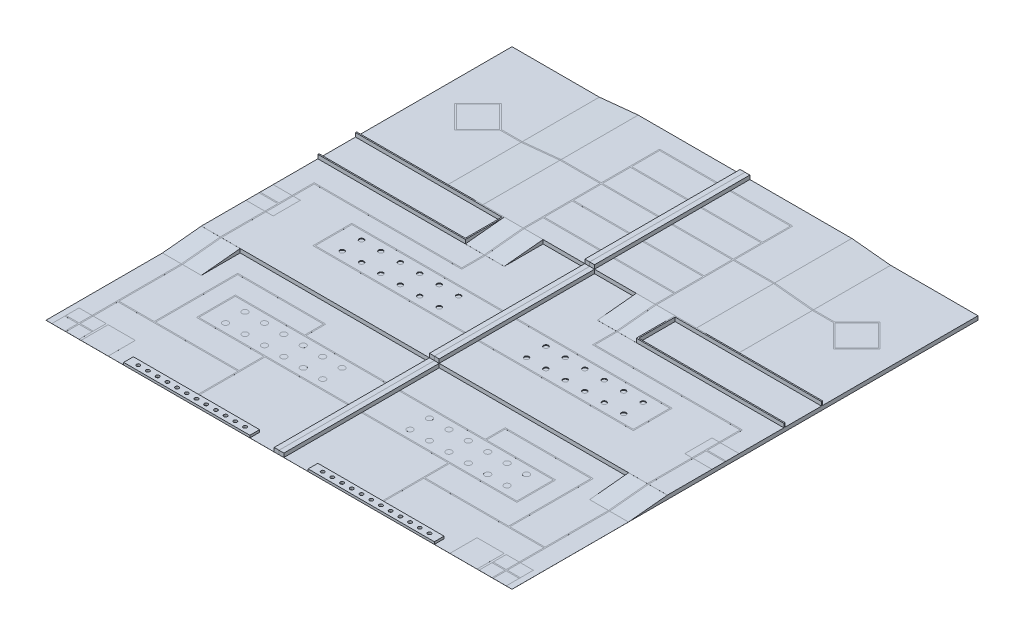
SolidWorks part; units mm, degrees
ref_plane "Front Plane" through (0, 0, 0) normal (0, 0, 1) x (1, 0, 0)
ref_plane "Top Plane" through (0, 0, 0) normal (0, 1, 0) x (1, 0, 0)
ref_plane "Right Plane" through (0, 0, 0) normal (1, 0, 0) x (0, 0, -1)
sketch "Sketch1" plane through (0, 0, 0) normal (0, 0, 1) x (1, 0, 0)
  line L0 (0, 0) -> (6000, 0)
  line L1 (6000, 0) -> (6000, 1)
  line L2 (6000, 1) -> (0, 1)
  line L3 (0, 1) -> (0, 0)
  dimension "D1" = 6000
  dimension "D2" = 1
extrude "Boss-Extrude1" add sketch "Sketch1" along normal mid plane 12000
sketch "Sketch15" plane through (0, 1, 0) normal (0, 1, 0) x (1, 0, 0)
  line L0 (0, 6000) -> (125, 6000)
  line L1 (6000, 6000) -> (0, 6000) construction
  line L2 (125, 6000) -> (125, -6000)
  line L3 (6000, -6000) -> (0, -6000) construction
  line L4 (125, -6000) -> (0, -6000)
  line L5 (0, -6000) -> (0, 6000)
  dimension "D1" = 125
extrude "Boss-Extrude5" add sketch "Sketch15" along normal blind 300 contours L2 L4 L5 L0
sketch "Sketch17" plane through (0, 1, 0) normal (0, 1, 0) x (1, 0, 0)
  line L0 (125, 6000) -> (6000, 6000)
  line L1 (6000, 6000) -> (6000, 2000)
  line L2 (6000, -6000) -> (6000, 6000) construction
  line L3 (6000, 2000) -> (125, 2000)
  line L4 (125, 6000) -> (125, -6000) construction
  line L5 (125, 2000) -> (125, 6000)
  dimension "D1" = 4000
extrude "Boss-Extrude6" add sketch "Sketch17" along normal blind 200 contours L3 L5 L0 L1
sketch "Sketch19" plane through (0, 1, 0) normal (0, 1, 0) x (1, 0, 0)
  line L0 (125, 2000) -> (6000, 2000)
  line L1 (6000, 2000) -> (6000, -2000)
  line L2 (6000, -6000) -> (6000, 2000) construction
  line L3 (6000, -2000) -> (125, -2000)
  line L4 (125, 2000) -> (125, -6000) construction
  line L5 (125, -2000) -> (125, 2000)
  dimension "D1" = 4000
extrude "Boss-Extrude7" add sketch "Sketch19" along normal blind 100 contours L3 L5 L0 L1
sketch "Sketch20" plane through (0, 1, 0) normal (0, 1, 0) x (1, 0, 0)
  line L0 (5150, -6000) -> (5150, -5300)
  line L1 (6000, -6000) -> (125, -6000) construction
  line L2 (5150, -5300) -> (5850, -5300)
  line L3 (5850, -5300) -> (5850, -6000)
  line L4 (5850, -6000) -> (5150, -6000)
  line L5 (6000, -6000) -> (6000, -2000) construction
  dimension "D1" = 700
  dimension "D2" = 700
  dimension "D3" = 150
extrude "Boss-Extrude8" add sketch "Sketch20" along normal blind 0.1
sketch "Sketch21" plane through (0, 1.1, 0) normal (0, 1, 0) x (1, 0, 0)
  line L0 (5485, -5300) -> (5515, -5300)
  line L1 (5850, -5300) -> (5150, -5300) construction
  line L2 (5515, -5300) -> (5515, -5635)
  line L3 (5515, -5635) -> (5850, -5635)
  line L4 (5850, -6000) -> (5850, -5300) construction
  line L5 (5850, -5635) -> (5850, -5665)
  line L6 (5850, -6000) -> (5850, -5300) construction
  line L7 (5850, -5665) -> (5515, -5665)
  line L8 (5515, -5665) -> (5515, -6000)
  line L9 (5150, -6000) -> (5850, -6000) construction
  line L10 (5515, -6000) -> (5485, -6000)
  line L11 (5485, -6000) -> (5485, -5665)
  line L12 (5485, -5665) -> (5150, -5665)
  line L13 (5150, -5300) -> (5150, -6000) construction
  line L14 (5150, -5665) -> (5150, -5635)
  line L15 (5150, -5300) -> (5150, -6000) construction
  line L16 (5150, -5635) -> (5485, -5635)
  line L17 (5485, -5635) -> (5485, -5300)
  line L18 (5850, -5300) -> (5150, -5300) construction
  dimension "D1" = 30
  dimension "D2" = 30
  dimension "D3" = 30
  dimension "D4" = 30
  dimension "D5" = 335
  dimension "D6" = 335
  dimension "D7" = 335
  dimension "D8" = 335
  dimension "D9" = 335
  dimension "D10" = 335
extrude "Boss-Extrude9" add sketch "Sketch21" along normal blind 0.1
sketch "Sketch23" plane through (0, 1, 0) normal (0, 1, 0) x (1, 0, 0)
  line L0 (5150, -6000) -> (125, -6000) construction
  line L1 (4400, -6000) -> (5100, -6000)
  line L2 (4400, -6000) -> (4400, -5300)
  line L3 (4400, -5300) -> (5100, -5300)
  line L4 (5100, -6000) -> (5100, -5300)
  line L5 (5150, -5300) -> (5150, -6000) construction
  dimension "D1" = 700
  dimension "D2" = 700
  dimension "D3" = 50
extrude "Boss-Extrude10" add sketch "Sketch23" along normal blind 0.1
sketch "Sketch24" plane through (0, 1, 0) normal (0, 1, 0) x (1, 0, 0)
  line L0 (4400, -6000) -> (125, -6000) construction
  line L1 (750, -6000) -> (4000, -6000)
  line L2 (750, -6000) -> (750, -5750)
  line L3 (750, -5750) -> (4000, -5750)
  line L4 (4000, -6000) -> (4000, -5750)
  line L5 (125, 6000) -> (125, -6000) construction
  line L6 (4400, -5300) -> (4400, -6000) construction
  point P6 (750, -5875)
  dimension "D1" = 3250
  dimension "D2" = 625
  dimension "D3" = 250
  dimension "D4" = 400
extrude "Boss-Extrude11" add sketch "Sketch24" along normal blind 60
sketch "Sketch25" plane through (0, 61, 0) normal (0, 1, 0) x (1, 0, 0)
  line L0 (4000, -5750) -> (750, -5750) construction
  line L1 (750, -6000) -> (4000, -6000) construction
  line L2 (750, -5750) -> (750, -6000) construction
  circle A0 centre (1000, -5875) radius 45
  circle A1 centre (1250, -5875) radius 45
  circle A2 centre (1500, -5875) radius 45
  circle A3 centre (1750, -5875) radius 45
  circle A4 centre (2000, -5875) radius 45
  circle A5 centre (2250, -5875) radius 45
  circle A6 centre (2500, -5875) radius 45
  circle A7 centre (2750, -5875) radius 45
  circle A8 centre (3000, -5875) radius 45
  circle A9 centre (3250, -5875) radius 45
  circle A10 centre (3500, -5875) radius 45
  circle A11 centre (3750, -5875) radius 45
  dimension "D4" = 90
  dimension "D1" = 125
  dimension "D2" = 125
  dimension "D3" = 250
  dimension "D6" = 250
  dimension "D7" = 125
  dimension "D8" = 250
  dimension "D9" = 250
  dimension "D5" = 12
extrude "Cut-Extrude2" cut sketch "Sketch25" against normal blind 59.5
sketch "Sketch26" plane through (0, 1, 0) normal (0, 1, 0) x (1, 0, 0)
  line L0 (2360, -5750) -> (2360, -4000)
  line L1 (4000, -5750) -> (750, -5750) construction
  line L2 (2360, -4000) -> (125, -4000)
  line L3 (125, -2000) -> (125, -6000) construction
  line L4 (125, -4000) -> (125, -3970)
  line L5 (125, -3970) -> (4095, -3970)
  line L6 (4095, -3970) -> (4095, -3030)
  line L7 (4095, -3030) -> (125, -3030)
  line L8 (125, -3030) -> (125, -3000)
  line L9 (125, -3000) -> (2310, -3000)
  line L10 (2310, -3000) -> (2310, -2485)
  line L11 (2310, -2485) -> (4578, -2485)
  line L12 (4578, -2485) -> (4578, -4635)
  line L13 (4578, -4635) -> (5485, -4635)
  line L14 (5485, -4635) -> (5485, -3000)
  line L15 (5485, -3000) -> (5515, -3000)
  line L16 (5515, -3000) -> (5515, -5300)
  line L18 (5515, -5300) -> (5485, -5300)
  line L20 (5485, -5300) -> (5485, -4665)
  line L21 (5485, -4665) -> (2390, -4665)
  line L22 (2390, -4665) -> (2390, -5750)
  line L23 (2390, -5750) -> (2360, -5750)
  line L24 (750, -5750) -> (750, -6000) construction
  line L25 (6000, -2000) -> (125, -2000) construction
  line L26 (6000, -2000) -> (125, -2000) construction
  line L27 (4000, -6000) -> (4000, -5750) construction
  line L28 (5100, -5300) -> (4400, -5300) construction
  line L29 (2390, -4000) -> (2390, -4635)
  line L30 (2390, -4635) -> (4548, -4635)
  line L31 (4548, -4635) -> (4548, -2515)
  line L32 (4548, -2515) -> (2340, -2515)
  line L33 (2340, -2515) -> (2340, -3000)
  line L34 (2340, -3000) -> (4125, -3000)
  line L35 (4125, -3000) -> (4125, -4000)
  line L36 (4125, -4000) -> (2390, -4000)
  line L39 (6000, -6000) -> (6000, -2000) construction
  line L40 (5850, -5300) -> (5150, -5300) construction
  line L41 (125, 6000) -> (125, -6000) construction
  point P19 (2360, -4875)
  dimension "D1" = 30
  dimension "D2" = 30
  dimension "D3" = 30
  dimension "D4" = 30
  dimension "D5" = 485
  dimension "D6" = 30
  dimension "D7" = 1610
  dimension "D8" = 2235
  dimension "D9" = 2185
  dimension "D10" = 485
  dimension "D11" = 1000
  dimension "D12" = 1750
  dimension "D13" = 1610
  dimension "D14" = 635
  dimension "D15" = 2635
  dimension "D16" = 2150
  dimension "D17" = 30
  dimension "D18" = 4000
  dimension "D19" = 30
  dimension "D20" = 30
  dimension "D21" = 30
  dimension "D22" = 30
  dimension "D23" = 30
  dimension "D24" = 30
  dimension "D25" = 30
  dimension "D26" = 2268
  dimension "D27" = 1785
  dimension "D28" = 423
  dimension "D29" = 2300
  dimension "D31" = 1360
extrude "Boss-Extrude15" add sketch "Sketch26" along normal blind 0.1 contours L18 L20 L21 L22 L23 L0 L2 L4 L5 L6 L7 L8 L9 L10 L11 L12 L13 L14 L15 L16
sketch "Sketch27" plane through (0, 1.1, 0) normal (0, 1, 0) x (1, 0, 0)
  line L0 (2340, -3000) -> (2340, -2515)
  line L1 (2340, -2515) -> (4548, -2515)
  line L2 (4548, -2515) -> (4548, -4635)
  line L3 (4548, -4635) -> (2390, -4635)
  line L4 (2390, -4635) -> (2390, -4000)
  line L5 (2390, -4000) -> (4125, -4000)
  line L6 (4125, -4000) -> (4125, -3000)
  line L7 (4125, -3000) -> (2340, -3000)
  line L8 (2310, -3000) -> (2310, -2485) construction
  line L9 (4095, -3030) -> (125, -3030) construction
  line L10 (4578, -2485) -> (4578, -4635) construction
  line L11 (4095, -3970) -> (4095, -3030) construction
  line L12 (125, -3970) -> (4095, -3970) construction
  line L13 (2360, -5750) -> (2360, -4000) construction
  line L14 (5485, -4665) -> (2390, -4665) construction
  line L15 (2310, -2485) -> (4578, -2485) construction
  dimension "D1" = 30
  dimension "D2" = 30
  dimension "D3" = 30
  dimension "D4" = 30
  dimension "D5" = 30
  dimension "D6" = 30
  dimension "D7" = 30
  dimension "D8" = 30
extrude "Cut-Extrude3" cut sketch "Sketch27" against normal blind 0.1
sketch "Sketch28" plane through (0, 1, 0) normal (0, 1, 0) x (1, 0, 0)
  line L1 (6000, -2000) -> (5000, -2000)
  line L2 (6000, -2000) -> (6000, -3000)
  line L3 (6000, -3000) -> (5000, -3000)
  line L4 (5000, -2000) -> (5000, -3000)
  dimension "D1" = 1000
  dimension "D2" = 1000
sketch "Sketch29" plane through (0, 1, 0) normal (0, 1, 0) x (1, 0, 0)
  line L0 (125, 6000) -> (125, -6000) construction
  line L1 (125, -3030) -> (125, -3970) construction
  line L2 (125, -3970) -> (4095, -3970) construction
  line L3 (4095, -3030) -> (125, -3030) construction
  line L4 (4095, -3970) -> (4095, -3030) construction
  circle A0 centre (1125, -3250) radius 75
  circle A1 centre (1125, -3750) radius 75
  circle A2 centre (1625, -3750) radius 75
  circle A3 centre (1625, -3250) radius 75
  circle A4 centre (2125, -3750) radius 75
  circle A5 centre (2125, -3250) radius 75
  circle A6 centre (2625, -3750) radius 75
  circle A7 centre (2625, -3250) radius 75
  circle A8 centre (3125, -3750) radius 75
  circle A9 centre (3125, -3250) radius 75
  circle A10 centre (3625, -3750) radius 75
  circle A11 centre (3625, -3250) radius 75
  dimension "D1" = 150
  dimension "D2" = 150
  dimension "D3" = 1000
  dimension "D4" = 1000
  dimension "D5" = 220
  dimension "D6" = 220
  dimension "D7" = 500
  dimension "D9" = 470
  dimension "D8" = 6
extrude "Boss-Extrude16" add sketch "Sketch28" along normal blind 99 contours L4 L3 L2 L1
chamfer "Chamfer1" distance 1000 angle 5.654 1 edges at (5500, 100, 3000) first distance on face at (5500, 100, 2500)
sketch "Sketch30" plane through (0, 295.1073, 29.2156) normal (0, 0.9951, 0.0985) x (1, 0, 0)
  line L0 (6000, -1980.4187) -> (5000, -1980.4187) construction
  line L1 (5485, -2985.3072) -> (5515, -2985.3072)
  line L2 (5485, -2985.3072) -> (5485, -1980.4187)
  line L3 (5485, -1980.4187) -> (5515, -1980.4187)
  line L4 (5515, -2985.3072) -> (5515, -1980.4187)
extrude "Boss-Extrude17" add sketch "Sketch30" along normal blind 0.1
sketch "Sketch31" plane through (0, 101, 0) normal (0, 1, 0) x (1, 0, 0)
  line L0 (125, 0) -> (4125, 0)
  line L1 (125, -2000) -> (125, 2000) construction
  line L2 (4125, 0) -> (4125, -1000)
  line L3 (4125, -1000) -> (125, -1000)
  line L4 (125, 6000) -> (125, -6000) construction
  line L5 (125, -1000) -> (125, -970)
  line L6 (125, -970) -> (4095, -970)
  line L7 (4095, -970) -> (4095, -30)
  line L8 (4095, -30) -> (125, -30)
  line L9 (125, -30) -> (125, 0)
  line L10 (6000, -2000) -> (125, -2000) construction
  line L11 (125, 2000) -> (6000, 2000) construction
  dimension "D1" = 30
  dimension "D2" = 30
  dimension "D3" = 30
  dimension "D4" = 1000
  dimension "D5" = 4000
  dimension "D6" = 1000
  dimension "D7" = 2000
sketch "Sketch32" plane through (0, 101, 0) normal (0, 1, 0) x (1, 0, 0)
  line L0 (6000, 2000) -> (6000, -2000) construction
  line L1 (6000, -850) -> (5300, -850)
  line L2 (6000, -850) -> (6000, -150)
  line L3 (6000, -150) -> (5300, -150)
  line L4 (5300, -850) -> (5300, -150)
  line L5 (6000, -2000) -> (125, -2000) construction
  dimension "D1" = 700
  dimension "D2" = 700
  dimension "D3" = 1150
extrude "Boss-Extrude18" add sketch "Sketch32" along normal blind 0.1
sketch "Sketch33" plane through (0, 101.1, 0) normal (0, 1, 0) x (1, 0, 0)
  line L0 (6000, -485) -> (6000, -515)
  line L1 (6000, -850) -> (6000, -150) construction
  line L2 (6000, -515) -> (5515, -515)
  line L3 (5515, -515) -> (5515, -850)
  line L4 (5300, -850) -> (6000, -850) construction
  line L5 (5515, -850) -> (5485, -850)
  line L6 (5300, -850) -> (6000, -850) construction
  line L7 (5485, -850) -> (5485, -150)
  line L8 (6000, -150) -> (5300, -150) construction
  line L9 (5485, -150) -> (5515, -150)
  line L10 (6000, -150) -> (5300, -150) construction
  line L11 (5515, -150) -> (5515, -485)
  line L12 (5515, -485) -> (6000, -485)
  line L14 (5300, -150) -> (5300, -850) construction
  point P4 (5485, -500)
  dimension "D1" = 30
  dimension "D2" = 30
  dimension "D3" = 485
  dimension "D4" = 335
  dimension "D5" = 335
  dimension "D6" = 185
extrude "Boss-Extrude19" add sketch "Sketch33" along normal blind 0.1
extrude "Boss-Extrude20" add sketch "Sketch31" along normal blind 0.1
extrude "Boss-Extrude21" add sketch "Sketch29" along normal blind 0.1
sketch "Sketch35" plane through (0, 101, 0) normal (0, 1, 0) x (1, 0, 0)
  line L0 (5485, -150) -> (5485, 390)
  line L1 (5485, -2000.0099) -> (5515, -2000.0099)
  line L2 (5485, -2000.0099) -> (5485, -850)
  line L3 (5485, -850) -> (5515, -850)
  line L4 (5515, -2000.0099) -> (5515, -850)
  line L5 (5485, 390) -> (1685, 390)
  line L6 (1685, 390) -> (1685, 1000)
  line L7 (1685, 1000) -> (1715, 1000)
  line L8 (1715, 1000) -> (1715, 420)
  line L9 (1715, 420) -> (5515, 420)
  line L10 (5515, 420) -> (5515, -150)
  line L11 (5515, -150) -> (5485, -150)
  line L12 (6000, 2000) -> (6000, -150) construction
  line L13 (125, 6000) -> (125, -6000) construction
  line L14 (125, 2000) -> (6000, 2000) construction
  line L16 (6000, 2000) -> (125, 2000) construction
  dimension "D1" = 30
  dimension "D2" = 30
  dimension "D3" = 30
  dimension "D4" = 30
  dimension "D5" = 485
  dimension "D6" = 4285
  dimension "D7" = 1560
  dimension "D8" = 1000
  dimension "D9" = 1580
  dimension "D10" = 4285
extrude "Boss-Extrude22" add sketch "Sketch35" along normal blind 0.1
sketch "Sketch36" plane through (0, 101, 0) normal (0, 1, 0) x (1, 0, 0)
  line L0 (6000, 2000) -> (125, 2000) construction
  line L1 (1200, 2000) -> (2200, 2000)
  line L2 (1200, 2000) -> (1200, 1000)
  line L3 (1200, 1000) -> (2200, 1000)
  line L4 (2200, 2000) -> (2200, 1000)
  line L5 (125, 0) -> (125, 2000) construction
  line L6 (6000, 2000) -> (6000, -150) construction
  dimension "D1" = 1000
  dimension "D2" = 1000
  dimension "D3" = 1075
  dimension "D4" = 3800
extrude "Boss-Extrude23" add sketch "Sketch36" along normal blind 100.01
sketch "Sketch37" plane through (0, 101, 0) normal (0, 1, 0) x (1, 0, 0)
  line L0 (6000, 1000) -> (2200, 1000)
  line L1 (6000, 2000) -> (6000, -150) construction
  line L2 (2200, 1000) -> (2200, 2000)
  line L3 (6000, 2000) -> (2200, 2000) construction
  line L4 (2200, 2000) -> (6000, 2000)
  line L5 (6000, 2000) -> (6000, 1970)
  line L6 (6000, 1970) -> (2230, 1970)
  line L7 (2230, 1970) -> (2230, 1030)
  line L8 (2230, 1030) -> (6000, 1030)
  line L9 (6000, 1030) -> (6000, 1000)
  dimension "D1" = 30
  dimension "D2" = 30
  dimension "D3" = 30
  dimension "D4" = 3800
  dimension "D5" = 1000
extrude "Boss-Extrude24" add sketch "Sketch37" along normal blind 100.1
chamfer "Chamfer2" distance 1000 angle 5.654 1 edges at (1700, 201.01, -1000) first distance on face at (1700, 201.01, -1500)
sketch "Sketch39" plane through (0, 2.9811, 0.2951) normal (0, 0.9951, 0.0985) x (1, 0, 0)
  line L0 (2200, 2010.0736) -> (1200, 2010.0736) construction
  line L1 (1685, 1005.0856) -> (1715, 1005.0856)
  line L2 (1685, 1005.0856) -> (1685, 2010.0736)
  line L3 (1685, 2010.0736) -> (1715, 2010.0736)
  line L4 (1715, 1005.0856) -> (1715, 2010.0736)
  line L5 (1715, 427.917) -> (1715, 1005.0954) construction
  dimension "D1" = 30
extrude "Boss-Extrude25" add sketch "Sketch39" along normal blind 0.1
sketch "Sketch40" plane through (0, 101, 0) normal (0, 1, 0) x (1, 0, 0)
  line L0 (125, 6000) -> (125, -6000) construction
  line L1 (125, -1000) -> (4125, -1000) construction
  line L2 (4125, 0) -> (125, 0) construction
  circle A0 centre (1125, -250) radius 60
  circle A1 centre (1125, -750) radius 60
  dimension "D1" = 120
  dimension "D2" = 120
  dimension "D3" = 1000
  dimension "D4" = 1000
  dimension "D5" = 250
  dimension "D6" = 250
  dimension "D7" = 500
extrude "Cut-Extrude4" cut sketch "Sketch40" against normal blind 20 contours A0 | A1
pattern_linear "LPattern1" count 6 spacing 500 along (1, 0, 0) of "Cut-Extrude4"
sketch "Sketch41" plane through (0, 201, 0) normal (0, 1, 0) x (1, 0, 0)
  line L0 (6000, 6000) -> (3750, 6000)
  line L1 (125, 6000) -> (6000, 6000) construction
  line L2 (3750, 6000) -> (3750, 2000)
  line L3 (6000, 2000) -> (2200, 2000) construction
  line L4 (3750, 2000) -> (6000, 2000)
  line L5 (6000, 2000) -> (6000, 6000)
  dimension "D1" = 2250
  dimension "D2" = 4000
extrude "Cut-Extrude5" cut sketch "Sketch41" against normal blind 100
chamfer "Chamfer4" distance 1000 angle 5.71 1 edges at (3750, 201, -4000) first distance on face at (1790, 201, -3600)
sketch "Sketch43" plane through (0, 201, 0) normal (0, 1, 0) x (1, 0, 0)
  line L0 (1685, 2000) -> (1685, 2485)
  line L1 (1685, 2485) -> (125, 2485)
  line L2 (125, 6000) -> (125, -6000) construction
  line L3 (125, 2485) -> (125, 2515)
  line L4 (125, 2515) -> (1685, 2515)
  line L5 (1685, 2515) -> (1685, 3235)
  line L6 (1685, 3235) -> (125, 3235)
  line L7 (125, 2000) -> (125, 6000) construction
  line L8 (125, 3235) -> (125, 3265)
  line L9 (125, 3265) -> (1685, 3265)
  line L10 (1685, 3265) -> (1685, 3985)
  line L11 (1685, 3985) -> (125, 3985)
  line L12 (125, 3985) -> (125, 4015)
  line L13 (125, 4015) -> (1685, 4015)
  line L14 (1685, 4015) -> (1685, 4735)
  line L15 (1685, 4735) -> (125, 4735)
  line L16 (125, 4735) -> (125, 4765)
  line L17 (125, 4765) -> (1685, 4765)
  line L18 (1685, 4765) -> (1685, 5485)
  line L19 (1685, 5485) -> (125, 5485)
  line L20 (125, 5485) -> (125, 5515)
  line L21 (125, 5515) -> (1715, 5515)
  line L22 (1715, 5515) -> (1715, 4015)
  line L23 (1715, 4015) -> (2750, 4015)
  line L24 (2750, 2000) -> (2750, 6000) construction
  line L25 (2750, 4015) -> (2750, 3985)
  line L26 (2750, 3985) -> (1715, 3985)
  line L27 (1715, 3985) -> (1715, 2000)
  line L29 (1715, 2000) -> (1685, 2000)
  line L30 (1200, 2000) -> (125, 2000) construction
  line L31 (125, 6000) -> (2750, 6000) construction
  line L32 (2750, 2000) -> (1200, 2000) construction
  dimension "D1" = 30
  dimension "D2" = 30
  dimension "D3" = 30
  dimension "D4" = 30
  dimension "D5" = 30
  dimension "D6" = 30
  dimension "D7" = 30
  dimension "D8" = 485
  dimension "D9" = 720
  dimension "D10" = 720
  dimension "D11" = 485
  dimension "D12" = 720
  dimension "D13" = 720
  dimension "D14" = 1035
  dimension "D15" = 1985
extrude "Boss-Extrude27" add sketch "Sketch43" along normal blind 0.01
sketch "Sketch44" plane through (47.121, 471.2596, 0) normal (0.0995, 0.995, 0) x (0.995, -0.0995, 0)
  line L0 (3721.3435, 6000) -> (3721.3435, 2000) construction
  line L1 (2716.3559, 4015) -> (3721.3435, 4015)
  line L2 (2716.3559, 4015) -> (2716.3559, 3985)
  line L3 (2716.3559, 3985) -> (3721.3435, 3985)
  line L4 (3721.3435, 4015) -> (3721.3435, 3985)
extrude "Boss-Extrude28" add sketch "Sketch44" along normal blind 0.01
sketch "Sketch45" plane through (0, 101, 0) normal (0, 1, 0) x (1, 0, 0)
  line L0 (3750.001, 4015) -> (3750, 3985)
  line L1 (3750, 6000) -> (3750, 2000) construction
  line L2 (125, 4015) -> (125, 3985) construction
  line L3 (3750, 3985) -> (4289.001, 3985)
  line L4 (4289.001, 3985) -> (4874.9185, 3399)
  line L5 (4874.9185, 3399) -> (5476, 4000)
  line L6 (5476, 4000) -> (4874.9185, 4601)
  line L7 (4874.9185, 4601) -> (4289.001, 4015)
  line L8 (4289.001, 4015) -> (3750.001, 4015)
  line L9 (3750.001, 3985) -> (3750.001, 4015) construction
  line L10 (3750.001, 4015) -> (2750, 4015) construction
  line L11 (3750, 4015) -> (2750, 4015) construction
  line L12 (2750, 3985) -> (3750, 3985) construction
  line L13 (3750, 2000) -> (6000, 2000) construction
  line L14 (6000, 2000) -> (6000, 6000) construction
  line L15 (4316.4265, 4000) -> (4316.4265, 4000)
  line L16 (4316.4265, 4000) -> (4316.4265, 4000)
  line L17 (4316.4265, 4000) -> (4316.4265, 4000)
  line L18 (4316.4265, 4000) -> (4874.9214, 3441.4265)
  line L19 (4874.9214, 3441.4265) -> (5433.5707, 4000)
  line L20 (5433.5707, 4000) -> (4874.9214, 4558.5735)
  line L21 (4874.9214, 4558.5735) -> (4316.4265, 4000)
  point P6 (125, 4000)
  dimension "D1" = 30
  dimension "D2" = 539
  dimension "D3" = 850
  dimension "D4" = 850
  dimension "D5" = 1202
  dimension "D6" = 1399
  dimension "D7" = 524
  dimension "D8" = 1186.999
  dimension "D9" = 828.6708
  dimension "D10" = 828.6708
  dimension "D11" = 30
extrude "Boss-Extrude30" add sketch "Sketch45" along normal blind 0.1 separate body
sketch "Sketch48" plane through (0, 301, 0) normal (0, 1, 0) x (1, 0, 0)
  line L1 (125, -2000) -> (0, -2000)
  line L2 (125, -2000) -> (125, -6000)
  line L3 (125, -6000) -> (0, -6000)
  line L4 (0, -2000) -> (0, -6000)
extrude "Cut-Extrude8" cut sketch "Sketch48" against normal blind 200
sketch "Sketch49" plane through (0, 301, 0) normal (0, 1, 0) x (1, 0, 0)
  line L0 (125, 6000) -> (125, -2000) construction
  line L1 (125, 2000) -> (0, 2000)
  line L2 (125, 2000) -> (125, -2000)
  line L3 (125, -2000) -> (0, -2000)
  line L4 (0, 2000) -> (0, -2000)
extrude "Cut-Extrude9" cut sketch "Sketch49" against normal blind 100
mirror "Mirror3" about plane through (0, 1, 6000) normal (1, 0, 0) of bodies 147 136 141
